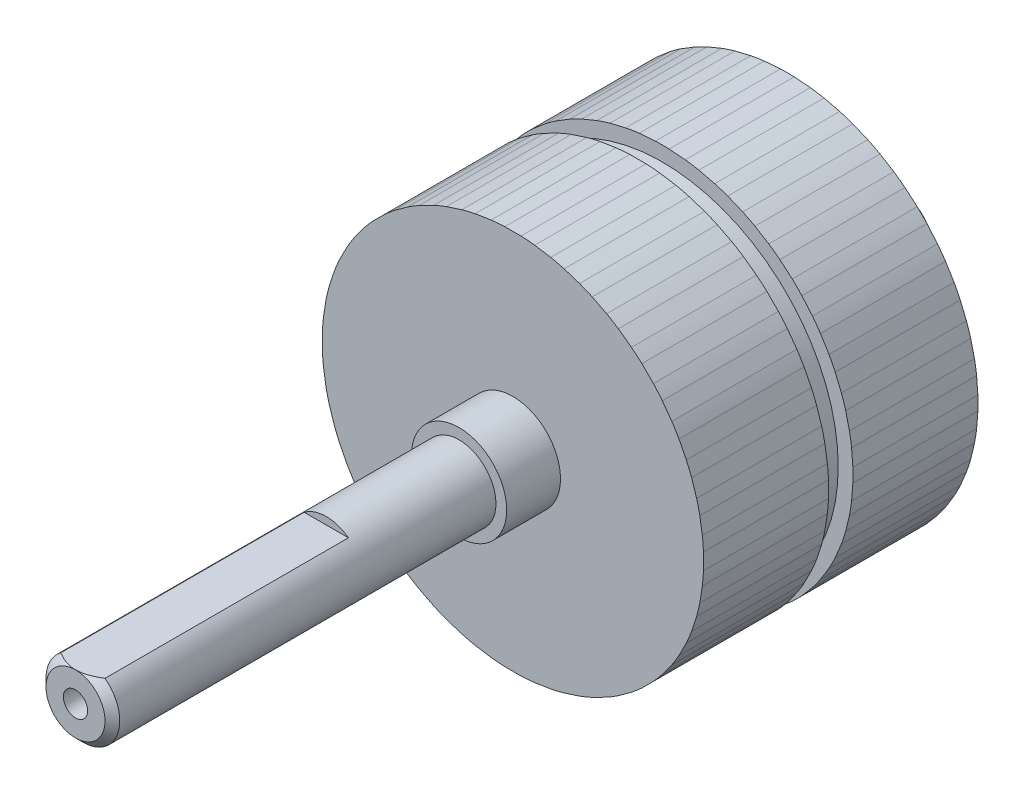
SolidWorks part; units mm, degrees
material "AISI Type A2 Tool Steel"
ref_plane "Front" through (0, 0, 0) normal (0, 0, 1) x (1, 0, 0)
ref_plane "Top" through (0, 0, 0) normal (0, 1, 0) x (1, 0, 0)
ref_plane "Right" through (0, 0, 0) normal (1, 0, 0) x (0, 0, -1)
sketch "Sketch1" plane through (0, 0, 0) normal (1, 0, 0) x (0, 0, -1)
  line L0 (-34.7383, 0) -> (0, 0) construction
  line L1 (0, 0) -> (0, 20.5789) construction
  line L2 (-28, -0.825) -> (-28, -2)
  line L3 (1.65, -12.925) -> (2.65, -11.925)
  line L4 (2.65, -11.925) -> (9.125, -11.925)
  line L5 (-28, -2) -> (-27.5, -2.5)
  line L6 (9.125, -11.925) -> (10.125, -12.925)
  line L7 (-27.5, -2.5) -> (-2, -2.5)
  line L8 (11.775, -12.925) -> (12.775, -11.925)
  line L9 (-2, -2.5) -> (-2, -3.225)
  line L10 (-2, -3.225) -> (1.65, -3.225)
  line L11 (1.65, -3.225) -> (1.65, -12.925)
  line L12 (1.65, -12.925) -> (10.125, -12.925)
  line L13 (10.125, -12.925) -> (10.125, -11.925)
  line L14 (12.775, -11.925) -> (19.25, -11.925)
  line L15 (10.125, -11.925) -> (11.775, -11.925)
  line L16 (19.25, -11.925) -> (20.25, -12.925)
  line L17 (11.775, -11.925) -> (11.775, -12.925)
  line L18 (11.775, -12.925) -> (20.25, -12.925)
  line L20 (20.25, -12.925) -> (20.25, -3.225)
  line L21 (20.25, -3.225) -> (23, -3.225)
  line L23 (23, -3.225) -> (23, -2.5)
  line L25 (23, -2.5) -> (27.5, -2.5)
  line L27 (27.5, -2.5) -> (28, -2)
  line L29 (28, -2) -> (28, -0.875)
  line L31 (28, -0.875) -> (26.5, -0.875)
  line L33 (26.5, -0.875) -> (26.5, 0)
  line L34 (26.5, 0) -> (-26.5, 0)
  line L36 (-26.5, 0) -> (-26.5, -0.825)
  line L37 (-26.5, -0.825) -> (-28, -0.825)
  dimension "D1" = 5
  dimension "D2" = 25.85
  dimension "D3" = 23.85
  dimension "D4" = 6.45
  dimension "D5" = 28
  dimension "D6" = 56
  dimension "D7" = 18.6
  dimension "D8" = 1.65
  dimension "D9" = 3.65
  dimension "D10" = 2.75
  dimension "D11" = 1.5
  dimension "D12" = 1.75
  dimension "D13" = 0.5
  dimension "D14" = 45
  dimension "D15" = 1.65
  dimension "D16" = 1.65
  dimension "D17" = 1.5
  dimension "D18" = 45
revolve "Revolve1" add sketch "Sketch1" angle 360 about L0 region at (0, -4.6233, -6.2106)
sketch "Sketch2" plane through (0, 0, -1.65) normal (0, 0, 1) x (1, 0, 0)
  line L0 (0, 0) -> (0, 12.9133) construction
  line L1 (4.957, 11.9672) -> (3.0239, 12.5953)
  line L2 (3.0239, 12.5953) -> (1.0163, 12.9133)
  line L3 (1.0163, 12.9133) -> (-1.0163, 12.9133)
  line L4 (-1.0163, 12.9133) -> (-3.0239, 12.5953)
  line L5 (-3.0239, 12.5953) -> (-4.957, 11.9672)
  line L6 (-4.957, 11.9672) -> (-6.768, 11.0444)
  line L7 (-6.768, 11.0444) -> (-8.4124, 9.8497)
  line L8 (-8.4124, 9.8497) -> (-9.8497, 8.4124)
  line L9 (-9.8497, 8.4124) -> (-11.0444, 6.768)
  line L10 (-11.0444, 6.768) -> (-11.9672, 4.957)
  line L11 (-11.9672, 4.957) -> (-12.5953, 3.0239)
  line L12 (-12.5953, 3.0239) -> (-12.9133, 1.0163)
  line L13 (-12.9133, 1.0163) -> (-12.9133, -1.0163)
  line L14 (-12.9133, -1.0163) -> (-12.5953, -3.0239)
  line L15 (-12.5953, -3.0239) -> (-11.9672, -4.957)
  line L16 (-11.9672, -4.957) -> (-11.0444, -6.768)
  line L17 (-11.0444, -6.768) -> (-9.8497, -8.4124)
  line L18 (-9.8497, -8.4124) -> (-8.4124, -9.8497)
  line L19 (-8.4124, -9.8497) -> (-6.768, -11.0444)
  line L20 (-6.768, -11.0444) -> (-4.957, -11.9672)
  line L21 (-4.957, -11.9672) -> (-3.0239, -12.5953)
  line L22 (-3.0239, -12.5953) -> (-1.0163, -12.9133)
  line L23 (-1.0163, -12.9133) -> (1.0163, -12.9133)
  line L24 (1.0163, -12.9133) -> (3.0239, -12.5953)
  line L25 (3.0239, -12.5953) -> (4.957, -11.9672)
  line L26 (4.957, -11.9672) -> (6.768, -11.0444)
  line L27 (6.768, -11.0444) -> (8.4124, -9.8497)
  line L28 (8.4124, -9.8497) -> (9.8497, -8.4124)
  line L29 (9.8497, -8.4124) -> (11.0444, -6.768)
  line L30 (11.0444, -6.768) -> (11.9672, -4.957)
  line L31 (11.9672, -4.957) -> (12.5953, -3.0239)
  line L32 (12.5953, -3.0239) -> (12.9133, -1.0163)
  line L33 (12.9133, -1.0163) -> (12.9133, 1.0163)
  line L34 (12.9133, 1.0163) -> (12.5953, 3.0239)
  line L35 (12.5953, 3.0239) -> (11.9672, 4.957)
  line L36 (11.9672, 4.957) -> (11.0444, 6.768)
  line L37 (11.0444, 6.768) -> (9.8497, 8.4124)
  line L38 (9.8497, 8.4124) -> (8.4124, 9.8497)
  line L39 (8.4124, 9.8497) -> (6.768, 11.0444)
  line L40 (6.768, 11.0444) -> (4.957, 11.9672)
  circle A0 centre (0, 0) radius 12.9133 construction
  circle A1 centre (0, 0) radius 12.925 construction
  circle A3 centre (0, 0) radius 12.925 construction
  point P45 (0.55, 12.9133)
  dimension "D1" = 0.55
revolve "Revolve2" add sketch "Sketch1<3>" angle 360 about L0 region at (0, -12.4473, -5.8875) region at (0, -12.4473, -16.0125)
sketch "Sketch1<3>" plane through (0, 0, 0) normal (1, 0, 0) x (0, 0, -1) same geometry as "Sketch1"
extrude "Cut-Extrude1" cut sketch "Sketch2" against normal up to surface (8.475 mm away) flip side to cut up to face at (11.925, 0, -10.125)
sketch "Sketch3" plane through (0, 0, -20.25) normal (0, 0, -1) x (-1, 0, 0)
  line L0 (0, 0) -> (1.0132, 12.8735) construction
  line L1 (0, 12.9532) -> (-2.0263, 12.7937)
  line L2 (-2.0263, 12.7937) -> (-4.0028, 12.3192)
  line L3 (-4.0028, 12.3192) -> (-5.8806, 11.5414)
  line L4 (-5.8806, 11.5414) -> (-7.6137, 10.4794)
  line L5 (-7.6137, 10.4794) -> (-9.1593, 9.1593)
  line L6 (-9.1593, 9.1593) -> (-10.4794, 7.6137)
  line L7 (-10.4794, 7.6137) -> (-11.5414, 5.8806)
  line L8 (-11.5414, 5.8806) -> (-12.3192, 4.0028)
  line L9 (-12.3192, 4.0028) -> (-12.7937, 2.0263)
  line L10 (-12.7937, 2.0263) -> (-12.9532, 0)
  line L11 (-12.9532, 0) -> (-12.7937, -2.0263)
  line L12 (-12.7937, -2.0263) -> (-12.3192, -4.0028)
  line L13 (-12.3192, -4.0028) -> (-11.5414, -5.8806)
  line L14 (-11.5414, -5.8806) -> (-10.4794, -7.6137)
  line L15 (-10.4794, -7.6137) -> (-9.1593, -9.1593)
  line L16 (-9.1593, -9.1593) -> (-7.6137, -10.4794)
  line L17 (-7.6137, -10.4794) -> (-5.8806, -11.5414)
  line L18 (-5.8806, -11.5414) -> (-4.0028, -12.3192)
  line L19 (-4.0028, -12.3192) -> (-2.0263, -12.7937)
  line L20 (-2.0263, -12.7937) -> (0, -12.9532)
  line L21 (0, -12.9532) -> (2.0263, -12.7937)
  line L22 (2.0263, -12.7937) -> (4.0028, -12.3192)
  line L23 (4.0028, -12.3192) -> (5.8806, -11.5414)
  line L24 (5.8806, -11.5414) -> (7.6137, -10.4794)
  line L25 (7.6137, -10.4794) -> (9.1593, -9.1593)
  line L26 (9.1593, -9.1593) -> (10.4794, -7.6137)
  line L27 (10.4794, -7.6137) -> (11.5414, -5.8806)
  line L28 (11.5414, -5.8806) -> (12.3192, -4.0028)
  line L29 (12.3192, -4.0028) -> (12.7937, -2.0263)
  line L30 (12.7937, -2.0263) -> (12.9532, 0)
  line L31 (12.9532, 0) -> (12.7937, 2.0263)
  line L32 (12.7937, 2.0263) -> (12.3192, 4.0028)
  line L33 (12.3192, 4.0028) -> (11.5414, 5.8806)
  line L34 (11.5414, 5.8806) -> (10.4794, 7.6137)
  line L35 (10.4794, 7.6137) -> (9.1593, 9.1593)
  line L36 (9.1593, 9.1593) -> (7.6137, 10.4794)
  line L37 (7.6137, 10.4794) -> (5.8806, 11.5414)
  line L38 (5.8806, 11.5414) -> (4.0028, 12.3192)
  line L39 (4.0028, 12.3192) -> (2.0263, 12.7937)
  line L40 (2.0263, 12.7937) -> (0, 12.9532)
  circle A0 centre (0, 0) radius 12.9133 construction
  circle A2 centre (0, 0) radius 12.925 construction
  circle A3 centre (0, 0) radius 12.925 construction
  point P45 (1.5615, 12.8303)
  dimension "D1" = 0.55
extrude "Cut-Extrude2" cut sketch "Sketch3" against normal up to surface (8.475 mm away) flip side to cut up to face at (12.925, 0, -11.775)
sketch "Sketch4" plane through (0, 0, 28) normal (0, 0, 1) x (1, 0, 0)
  line L0 (-5.2183, -2.5) -> (10.7778, -2.5) construction
  line L1 (-2.5, 3) -> (2.5, 3)
  line L2 (-2.5, 3) -> (-2.5, 2)
  line L3 (-2.5, 2) -> (2.5, 2)
  line L4 (2.5, 3) -> (2.5, 2)
  line L5 (0, 0) -> (0, 6.0314) construction
  circle A0 centre (0, 0) radius 2.5 construction
  circle A1 centre (0, 0) radius 2.5 construction
  dimension "D1" = 4.5
  dimension "D2" = 1
extrude "Cut-Extrude3" cut sketch "Sketch4" against normal blind 17
